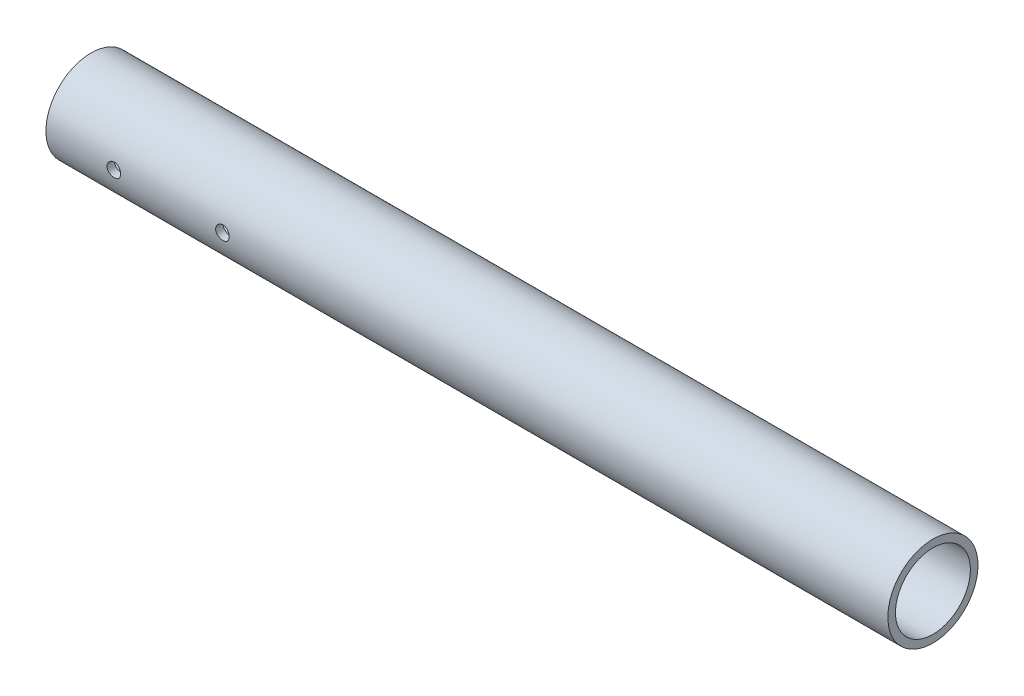
SolidWorks part; units mm, degrees
material "6061-T6 (SS)"
ref_plane "Front Plane" through (0, 0, 0) normal (0, 0, 1) x (1, 0, 0)
ref_plane "Top Plane" through (0, 0, 0) normal (0, 1, 0) x (1, 0, 0)
ref_plane "Right Plane" through (0, 0, 0) normal (1, 0, 0) x (0, 0, -1)
sketch "Sketch1" plane through (0, 0, 0) normal (1, 0, 0) x (0, 0, -1)
  circle A0 centre (0, 0) radius 21.082
  circle A1 centre (0, 0) radius 17.526
  dimension "D1" = 42.164
  dimension "D2" = 35.052
extrude "Boss-Extrude1" add sketch "Sketch1" along normal blind 196.85 and the other way blind 196.85
sketch "Sketch2" plane through (0, 0, 0) normal (0, 0, 1) x (1, 0, 0)
  line L0 (-196.85, 21.082) -> (-196.85, -21.082) construction
  circle A0 centre (-114.3, 0) radius 3.175
  circle A1 centre (-165.1, 0) radius 3.175
  dimension "D1" = 6.35
  dimension "D2" = 31.75
  dimension "D3" = 50.8
extrude "Cut-Extrude1" cut sketch "Sketch2" along normal through all
